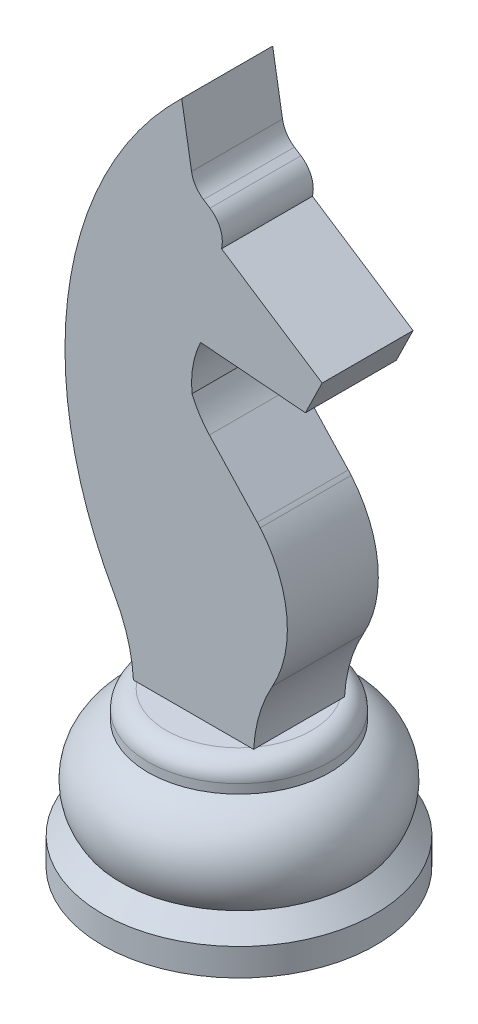
SolidWorks part; units mm, degrees
ref_plane "Front Plane" through (0, 0, 0) normal (0, 0, 1) x (1, 0, 0)
ref_plane "Top Plane" through (0, 0, 0) normal (0, 1, 0) x (1, 0, 0)
ref_plane "Right Plane" through (0, 0, 0) normal (1, 0, 0) x (0, 0, -1)
sketch "Sketch1" plane through (0, 0, 0) normal (0, 0, 1) x (1, 0, 0)
  line L0 (0, 0) -> (0, 37.6079) construction
  line L1 (0, 0) -> (-15, 0)
  line L2 (-15, 0) -> (-15, 3)
  line L3 (-15, 3) -> (-13, 5)
  line L4 (-10, 13.97) -> (-10, 14.97)
  line L5 (-8, 16.97) -> (0, 16.97)
  line L6 (0, 16.97) -> (0, 0)
  arc A0 (-13, 5) -> (-10, 13.97) centre (-7.9981, 8.3138) cw
  arc A1 (-10, 14.97) -> (-8, 16.97) centre (-8, 14.97) cw
  dimension "D7" = 6
  dimension "D9" = 2
  dimension "D1" = 30
  dimension "D2" = 26
  dimension "D3" = 2
  dimension "D4" = 3
  dimension "D5" = 8.97
  dimension "D6" = 20
  dimension "D8" = 1
  dimension "D10" = 16
revolve "Revolve1" add sketch "Sketch1" angle 360 about L0
sketch "Sketch2" plane through (0, 0, 0) normal (0, 0, 1) x (1, 0, 0)
  line L0 (0, 0) -> (0, 110.7526) construction
  line L1 (-15, 0) -> (15, 0) construction
  line L2 (8, 16.97) -> (-8, 16.97) construction
  line L3 (-6.61, 16.97) -> (6.61, 16.97)
  line L4 (-1.2956, 75) -> (0, 67.29)
  line L5 (0, 67.29) -> (4.18, 64.56)
  line L6 (4.18, 64.56) -> (3.08, 62.88)
  line L7 (3.08, 62.88) -> (14.14, 55.62)
  line L8 (14.14, 55.62) -> (12.3, 51.87)
  line L9 (12.3, 51.87) -> (0.78, 52.81)
  line L10 (0.78, 52.81) -> (-1, 50.32)
  line L11 (-1, 50.32) -> (0, 46.35)
  line L12 (0, 46.35) -> (7.12, 38.68)
  arc A0 (-6.61, 16.97) -> (-8.67, 24.01) centre (-22.6266, 16.1047) ccw
  arc A1 (6.61, 16.97) -> (8.67, 24.01) centre (22.6266, 16.1047) cw
  arc A2 (-8.67, 24.01) -> (-1.2956, 75) centre (27.9357, 44.7442) cw
  arc A3 (7.12, 38.68) -> (8.67, 24.01) centre (-2.362, 30.2613) cw
  dimension "D2" = 16.04
  dimension "D6" = 42.07
  dimension "D23" = 12.68
  dimension "D1" = 7.04
  dimension "D3" = 8.67
  dimension "D4" = 6.61
  dimension "D5" = 75
  dimension "D7" = 50.32
  dimension "D8" = 47.59
  dimension "D9" = 4.18
  dimension "D10" = 3.08
  dimension "D11" = 45.91
  dimension "D12" = 14.14
  dimension "D13" = 38.65
  dimension "D14" = 34.9
  dimension "D15" = 12.3
  dimension "D16" = 0.78
  dimension "D17" = 35.84
  dimension "D18" = 1
  dimension "D19" = 33.35
  dimension "D20" = 29.38
  dimension "D21" = 7.12
  dimension "D22" = 21.71
extrude "Boss-Extrude1" add sketch "Sketch2" along normal mid plane 10
fillet "Fillet1" radius 3 1 edges at (0, 67.29, 0)
fillet "Fillet2" radius 10 3 edges at (-1, 50.32, 0) (0, 46.35, 0) (7.12, 38.68, 0)
fillet "Fillet3" radius 3 1 edges at (4.18, 64.56, 0)
